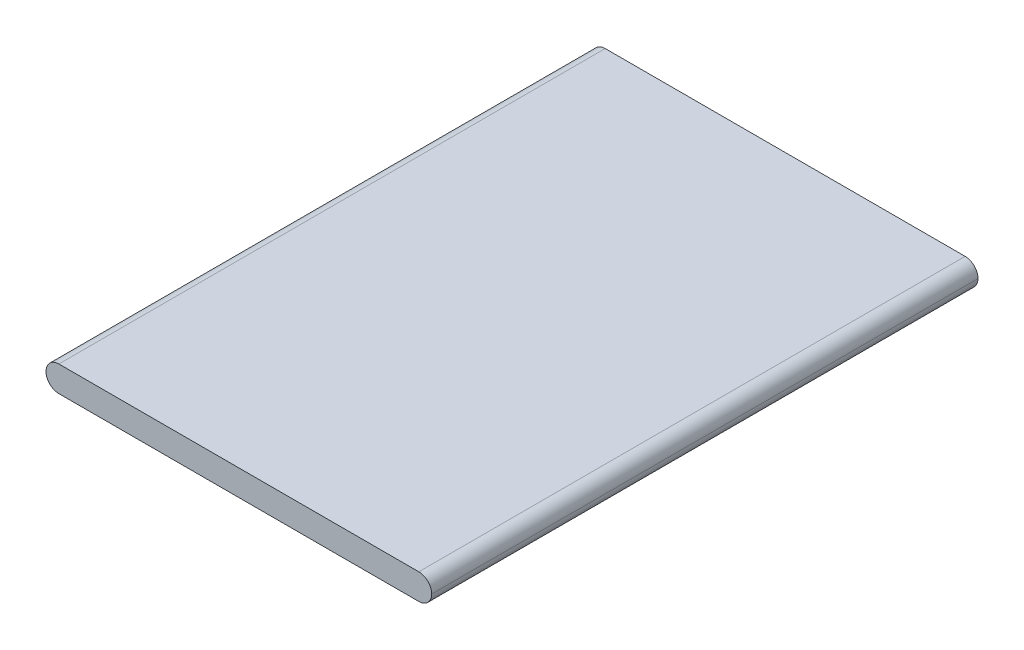
SolidWorks part; units mm, degrees
ref_plane "Front" through (0, 0, 0) normal (0, 0, 1) x (1, 0, 0)
ref_plane "Top" through (0, 0, 0) normal (0, 1, 0) x (1, 0, 0)
ref_plane "Right" through (0, 0, 0) normal (1, 0, 0) x (0, 0, -1)
sketch "Sketch2" plane through (0, 0, 0) normal (0, 1, 0) x (1, 0, 0)
  line L1 (-30, 42.5) -> (30, 42.5)
  line L2 (-30, 42.5) -> (-30, -42.5)
  line L3 (-30, -42.5) -> (30, -42.5)
  line L4 (30, 42.5) -> (30, -42.5)
  line L5 (-30, 42.5) -> (30, -42.5) construction
  line L6 (-30, -42.5) -> (30, 42.5) construction
  point P0 (0, 0)
  dimension "D1" = 60
  dimension "D2" = 85
extrude "Boss-Extrude1" add sketch "Sketch2" along normal blind 4
fillet "Fillet1" radius 2 4 edges at (30, 0, 0) (-30, 0, 0) (-30, 4, 0) (30, 4, 0)
